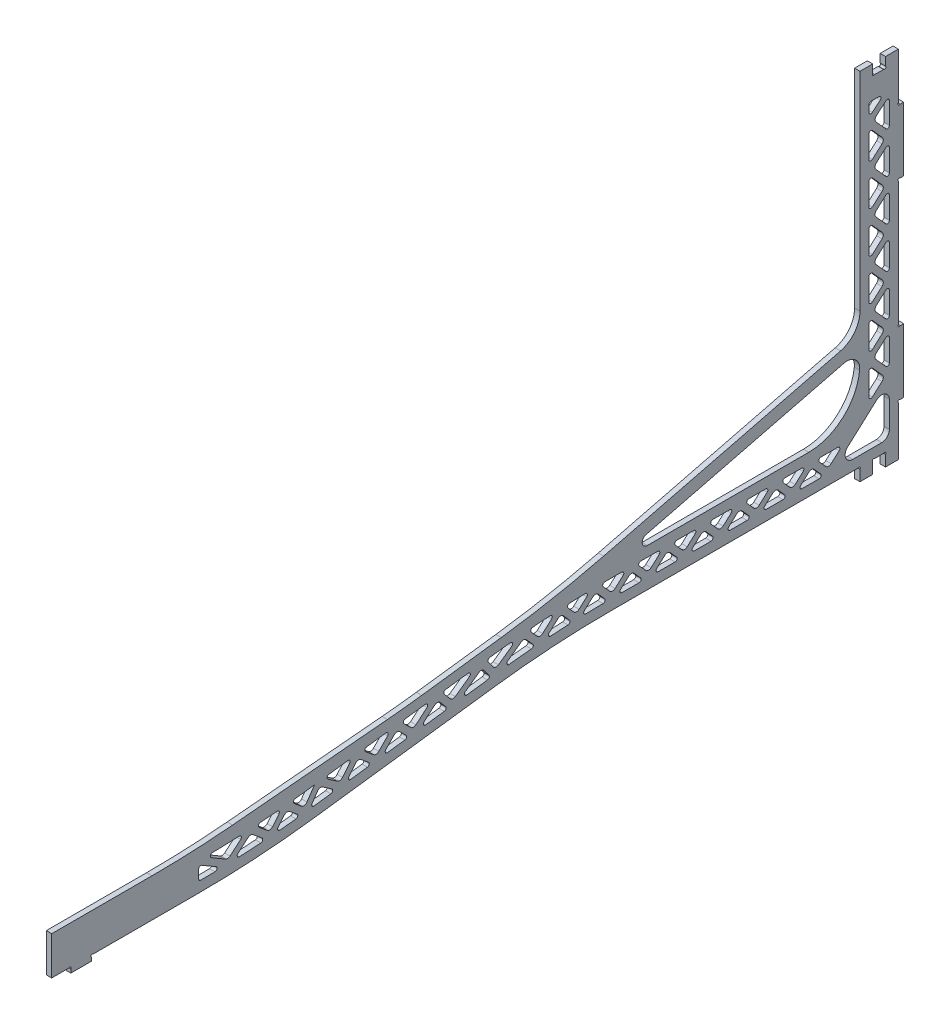
SolidWorks part; units mm, degrees
material "自定义塑料碳纤维-1.6"
ref_plane "前视基准面" through (0, 0, 0) normal (0, 0, 1) x (1, 0, 0)
ref_plane "上视基准面" through (0, 0, 0) normal (0, 1, 0) x (1, 0, 0)
ref_plane "右视基准面" through (0, 0, 0) normal (1, 0, 0) x (0, 0, -1)
other "Configuration Table"
sketch "草图2" plane through (0, 0, 0) normal (1, 0, 0) x (0, 0, -1)
  line L0 (0, 0) -> (331, 0)
  line L1 (331, 0) -> (331, 130)
  line L2 (331, 130) -> (316, 130)
  line L3 (316, 130) -> (316, 15)
  line L4 (316, 15) -> (0, 15)
  line L5 (0, 15) -> (0, 0)
  line L6 (331, 0) -> (331, -5)
  line L7 (331, -5) -> (326, -5)
  line L8 (326, -5) -> (326, 0)
  line L9 (321, 0) -> (321, -5)
  line L10 (321, -5) -> (316, -5)
  line L11 (316, -5) -> (316, 0)
  line L12 (331, 130) -> (331, 134)
  line L13 (331, 134) -> (326, 134)
  line L14 (326, 134) -> (326, 130)
  line L15 (80, 0) -> (196, 15)
  line L16 (196, 15) -> (196, 0) construction
  line L17 (196, 0) -> (80, -15)
  line L18 (80, -15) -> (0, -15)
  line L19 (0, -15) -> (0, 0)
  line L20 (80, 0) -> (80, -15) construction
  line L21 (55, 0) -> (138, 7.5)
  line L22 (316, 130) -> (316, 134)
  line L23 (316, 134) -> (321, 134)
  line L24 (321, 134) -> (321, 130)
  dimension "D1" = 15
  dimension "D2" = 130
  dimension "D3" = 15
  dimension "D4" = 331
  dimension "D5" = 4
  dimension "D6" = 5
  dimension "D7" = 5
  dimension "D8" = 5
  dimension "D9" = 5
  dimension "D10" = 5
  dimension "D11" = 120
  dimension "D12" = 15
  dimension "D13" = 80
  dimension "D14" = 25
  dimension "D15" = 5
extrude "凸台-拉伸1" add sketch "草图2" along normal mid plane 2.1 contours L19 L18 L17 L0 | L15 L0 L1 L2 L3 L4 | L13 L14 L2 L12 | L8 L7 L6 L0 | L11 L10 L9 L0 | L21 L0 L15 | L24 L23 L22 L2 region at (0, -6.4493, -73.0628) region at (0, 2.5, -91) region at (0, 0.9467, -109.3625) region at (0, -2.5, -318.5) region at (0, 132, -318.5) region at (0, -2.5, -328.5) region at (0, 132, -328.5)
sketch "草图3" plane through (1.05, 0, 0) normal (1, 0, 0) x (0, 0, -1)
  line L0 (331, 40) -> (333.1, 40)
  line L1 (331, -5) -> (331, 134) construction
  line L2 (333.1, 40) -> (333.1, 15)
  line L3 (333.1, 15) -> (331, 15)
  line L4 (331, 115) -> (333.1, 115)
  line L5 (331, -5) -> (331, 134) construction
  line L6 (333.1, 115) -> (333.1, 90)
  line L7 (333.1, 90) -> (331, 90)
  line L8 (331, 90) -> (331, 115)
  line L9 (331, 40) -> (331, 15)
  line L10 (316, 130) -> (316, 0)
  line L11 (331, 65) -> (316, 65)
  line L12 (331, 90) -> (331, 40)
  line L13 (326, 130) -> (316, 130)
  line M10 (331, -5) -> (331, 134)
  dimension "D2" = 50
  dimension "D3" = 25
  dimension "D4" = 25
  dimension "D5" = 2.1
extrude "凸台-拉伸2" add sketch "草图3" against normal up to surface (2.1 mm away) contours L7 L6 L4 M10 | L3 L2 L0 M10 region at (1.05, 27.5, -332.05) region at (1.05, 102.5, -332.05) up to face at (-1.05, 37.3095, -246.619)
fillet "圆角1" radius 20 1 edges at (0, 15, -316)
sketch "草图5" plane through (-1.05, 0, 0) normal (-1, 0, 0) x (0, 0, 1)
  line L0 (-316, 45) -> (-196, 15)
  line L1 (-316, 134) -> (-316, 35) construction
  line L2 (-296, 15) -> (-196, 15) construction
  dimension "D1" = 120
  dimension "D2" = 30
extrude "拉伸-薄壁1" add sketch "草图5" against normal up to surface (2.1 mm away) thin up to face at (1.05, 44.4786, -271.1847) thin type one direction wall 5
fillet "圆角2" radius 10 1 edges at (0, 45, -316)
fillet "圆角3" radius 5 1 edges at (0, 39.8461, -316)
fillet "圆角4" radius 2 1 edges at (0, 15, -216.6155)
fillet "圆角5" radius 350 5 edges at (0, 15, -196) (0, -15, -80) (0, 0, -196) (0, 7.5, -138) (0, 0, -55)
sketch "草图6" plane through (1.05, 0, 0) normal (1, 0, 0) x (0, 0, -1)
  line L0 (316, 130) -> (331, 130) construction
  line L1 (319.5, 121.6838) -> (327.5, 121.6838)
  line L2 (319.5, 121.6838) -> (319.5, 10)
  line L3 (319.5, 10) -> (327.5, 10)
  line L4 (327.5, 121.6838) -> (327.5, 10)
  line L5 (323.5, 10) -> (323.5, 121.6838) construction
  line L6 (319.5, 65.8419) -> (327.5, 65.8419) construction
  line L7 (331, 115) -> (331, 134) construction
  line L8 (323.5, 121.6838) -> (323.5, 130) construction
  line L9 (218.5355, 0) -> (316, 0) construction
  line L10 (316, 134) -> (316, 52.8078) construction
  line L11 (326, 130) -> (321, 130) construction
  point P0 (323.5, 65.8419)
  dimension "D1" = 8
  dimension "D2" = 8.3162
  dimension "D3" = 10
extrude "切除-拉伸1" cut sketch "草图6" against normal blind 10
sketch "草图7" plane through (1.05, 0, 0) normal (1, 0, 0) x (0, 0, -1)
  line L34 (316, 11) -> (218.5355, 11)
  line L35 (172.2399, 8.0192) -> (100.9387, -1.2008)
  line L36 (57.4645, -4) -> (0, -4)
  line L37 (316, 4) -> (218.5355, 4)
  line L38 (173.1376, 1.077) -> (101.8364, -8.143)
  line L39 (57.4645, -11) -> (0, -11)
  line L40 (316, 4) -> (218.5355, 4)
  line L41 (173.1376, 1.077) -> (101.8364, -8.143)
  line L42 (57.4645, -11) -> (0, -11)
  line L43 (309.5, 11) -> (319.5, 20)
  line L44 (319.5, 121.6838) -> (319.5, 10) construction
  line L45 (327.5, 10) -> (327.5, 4)
  line L46 (327.5, 4) -> (316, 4)
  line L47 (319.5, 10) -> (327.5, 10) construction
  line L48 (327.5, 10) -> (319.5, 20)
  line L49 (57.4645, -4) -> (57.4645, -11)
  arc A12 (218.5355, 11) -> (172.2399, 8.0192) centre (218.5355, -350) ccw
  arc A13 (57.4645, -4) -> (100.9387, -1.2008) centre (57.4645, 335) ccw
  arc A18 (218.5355, 4) -> (173.1376, 1.077) centre (218.5355, -350) ccw
  arc A19 (57.4645, -11) -> (101.8364, -8.143) centre (57.4645, 335) ccw
  arc A20 (218.5355, 4) -> (173.1376, 1.077) centre (218.5355, -350) ccw
  arc A21 (57.4645, -11) -> (101.8364, -8.143) centre (57.4645, 335) ccw
  line M28 (327.5, 10) -> (319.5, 10)
  line M29 (319.5, 10) -> (319.5, 121.6838)
  dimension "D3" = 10
  dimension "D4" = 10
  dimension "D1" = 4
  dimension "D2" = 7
extrude "切除-拉伸2" cut sketch "草图7" against normal blind 10 contours L49 A21 L41 A20 L40 L46 L45 L43 L34 A12 L35 A13 M28 M29 region at (1.05, 3.2645, -194.6514)
sketch "草图8" plane through (1.05, 0, 0) normal (1, 0, 0) x (0, 0, -1)
  line L0 (303.516, 4) -> (327.5, 25.5856)
  line L1 (327.5, 4) -> (327.5, 121.6838) construction
  line L2 (327.5, 25.5856) -> (319.5, 34.4745)
  line L3 (319.5, 121.6838) -> (319.5, 20) construction
  line L4 (319.5, 34.4745) -> (327.5, 41.6745)
  line L5 (327.5, 41.6745) -> (319.5, 50.5633)
  line L6 (319.5, 50.5633) -> (327.5, 57.7633)
  line L7 (327.5, 57.7633) -> (319.5, 66.6522)
  line L8 (319.5, 66.6522) -> (327.5, 73.8522)
  line L9 (327.5, 73.8522) -> (319.5, 82.7411)
  line L10 (319.5, 82.7411) -> (327.5, 89.9411)
  line L11 (327.5, 89.9411) -> (319.5, 98.83)
  line L12 (319.5, 98.83) -> (327.5, 106.03)
  line L13 (327.5, 106.03) -> (319.5, 114.9189)
  line L14 (319.5, 114.9189) -> (327.5, 121.6838)
  line L15 (57.4645, -4) -> (57.4645, -11) construction
  line L16 (309.5, 11) -> (319.5, 20) construction
  line L18 (327.5, 4) -> (218.5355, 4) construction
  line L19 (303.516, 4) -> (297.216, 11)
  line L20 (309.5, 11) -> (218.5355, 11) construction
  line L21 (297.216, 11) -> (289.4383, 4)
  line L22 (289.4383, 4) -> (283.1383, 11)
  line L23 (283.1383, 11) -> (275.3605, 4)
  line L24 (275.3605, 4) -> (269.0605, 11)
  line L25 (269.0605, 11) -> (261.2827, 4)
  line L26 (261.2827, 4) -> (254.9827, 11)
  line L27 (254.9827, 11) -> (247.2049, 4)
  line L28 (247.2049, 4) -> (240.9049, 11)
  line L29 (240.9049, 11) -> (233.1271, 4)
  line L30 (233.1271, 4) -> (226.8271, 11)
  line L31 (226.8271, 11) -> (219.0494, 4)
  line L32 (219.0494, 4) -> (212.7494, 11)
  line L33 (212.7494, 11) -> (204.9716, 4)
  line L34 (204.9716, 4) -> (199.1408, 10.4786)
  line L35 (199.1408, 10.4786) -> (190.7268, 2.906)
  line L36 (190.7268, 2.906) -> (184.8591, 9.4258)
  line L37 (184.8591, 9.4258) -> (173.1376, 1.077)
  line L38 (173.1376, 1.077) -> (168.5469, 7.5222)
  line L39 (168.5469, 7.5222) -> (156.4724, -1.078)
  line L40 (156.4724, -1.078) -> (151.0504, 5.2791)
  line L41 (151.0504, 5.2791) -> (141.2959, -3.0405)
  line L42 (141.2959, -3.0405) -> (134.9562, 3.198)
  line L43 (134.9562, 3.198) -> (126.998, -4.8894)
  line L44 (126.998, -4.8894) -> (119.6055, 1.213)
  line L45 (119.6055, 1.213) -> (113.0828, -6.6888)
  line L46 (173.1376, 1.077) -> (101.8364, -8.143) construction
  line L47 (113.0828, -6.6888) -> (104.4497, -0.7468)
  line L48 (172.2399, 8.0192) -> (100.9387, -1.2008) construction
  line L49 (104.4497, -0.7468) -> (99.117, -8.4947)
  line L50 (99.117, -8.4947) -> (91.7245, -2.3923)
  line L51 (91.7245, -2.3923) -> (85.5624, -9.8572)
  line L52 (85.5624, -9.8572) -> (77.7322, -3.3936)
  line L53 (77.7322, -3.3936) -> (69.0411, -10.8063)
  line L54 (69.0411, -10.8063) -> (57.4645, -4)
  arc A0 (218.5355, 4) -> (173.1376, 1.077) centre (218.5355, -350) ccw construction
  arc A1 (218.5355, 11) -> (172.2399, 8.0192) centre (218.5355, -350) ccw construction
  arc A2 (57.4645, -4) -> (100.9387, -1.2008) centre (57.4645, 335) ccw construction
  arc A3 (57.4645, -11) -> (101.8364, -8.143) centre (57.4645, 335) ccw construction
  dimension "D2" = 1.2
  dimension "D3" = 100
  dimension "D4" = 90
  dimension "D5" = 85
  dimension "D6" = 95
  dimension "D7" = 95
  dimension "D8" = 95
  dimension "D9" = 95
extrude "拉伸-薄壁2" add sketch "草图8" against normal up to surface (2.1 mm away) thin up to face at (-1.05, 39.8176, -251.717) thin type mid plane wall 2.5
fillet "圆角6" radius 3 3 edges at (0, 4, -327.5) (0, 4, -305.3846) (0, 23.9039, -327.5)
fillet "圆角7" radius 0.8 27 edges at (0, 121.6838, -319.5) (0, 113.0503, -319.5) (0, 96.9615, -319.5) (0, 80.8726, -319.5) (0, 64.7837, -319.5) (0, 48.6948, -319.5) (0, 107.8986, -327.5) (0, 91.8097, -327.5) (0, 75.7208, -327.5) (0, 59.6319, -327.5) (0, 43.543, -327.5) (0, 116.5559, -319.5) (0, 100.5117, -319.5) (0, 84.4228, -319.5) (0, 68.3339, -319.5) (0, 52.245, -319.5) (0, 36.1562, -319.5) (0, 120.0468, -327.5) (0, 104.3483, -327.5) (0, 88.2594, -327.5) (0, 72.1705, -327.5) (0, 56.0816, -327.5) (0, 39.9928, -327.5) (0, 32.6059, -319.5) (0, 27.4541, -327.5) (0, 20.0673, -319.5) (0, 121.6838, -325.5641)
fillet "圆角8" radius 1.5 12 edges at (0, 90.034, -325.7347) (0, 73.9451, -325.7347) (0, 57.8563, -325.7347) (0, 41.7674, -325.7347) (0, 50.4704, -321.2653) (0, 66.5593, -321.2653) (0, 82.6482, -321.2653) (0, 98.7371, -321.2653) (0, 106.1229, -325.7347) (0, 114.7969, -321.2915) (0, 25.6785, -325.7347) (0, 34.3815, -321.2653)
fillet "圆角9" radius 0.8 68 edges at (0, 4, -263.1513) (0, 4, -277.229) (0, 4, -291.3068) (0, 4, -249.0735) (0, 4, -234.9957) (0, 4, -220.9179) (0, 3.7993, -206.6172) (0, 1.4053, -175.7532) (0, 3.0609, -192.7675) (0, -0.7376, -159.105) (0, -2.7469, -143.5664) (0, -4.6295, -129.0074) (0, -6.4541, -114.8973) (0, -9.7109, -87.3041) (0, -10.7331, -71.0532) (0, -10.8769, -66.6949) (0, -9.9986, -83.7701) (0, -6.9288, -111.2267) (0, -5.1089, -125.3004) (0, -3.2442, -139.7208) (0, -1.2694, -154.9927) (0, 0.8952, -171.7324) (0, 2.779, -189.1594) (0, 3.6837, -203.5745) (0, 4, -231.4454) (0, 4, -245.5232) (0, 4, -259.601) (0, 4, -273.6788) (0, 4, -287.7566) (0, 4, -301.8343) (0, 11, -284.82) (0, 11, -298.8977) (0, 11, -270.7422) (0, 11, -256.6644) (0, 11, -242.5866) (0, 11, -228.5089) (0, 10.9769, -214.4519) (0, 10.5615, -200.7479) (0, 9.568, -186.4128) (0, 7.7217, -169.9394) (0, 5.4705, -152.5301) (0, 3.4017, -136.5314) (0, 1.4325, -121.3031) (0, -0.5068, -106.3058) (0, -2.0973, -93.3307) (0, -3.2793, -79.5574) (0, -3.9911, -59.9158) (0, -3.5109, -75.6685) (0, -2.4279, -90.0743) (0, 0.9783, -117.7909) (0, 2.9382, -132.9468) (0, 4.9855, -148.7799) (0, 7.2055, -165.9476) (0, 9.1833, -182.364) (0, 10.3658, -197.1469) (0, 10.9169, -210.7884) (0, 11, -224.9586) (0, 11, -239.0364) (0, 11, -253.1141) (0, 11, -267.1919) (0, 11, -281.2697) (0, 11, -295.3475) (0, 11, -309.4253) (0, 3.9981, -217.3694) (0, -8.6889, -97.3888) (0, -8.2775, -100.784) (0, -11, -57.4645) (0, -5.45, -57.4645)
fillet "圆角10" radius 1.5 33 edges at (0, 9.2347, -283.0453) (0, 9.2347, -297.1231) (0, 9.2347, -268.9676) (0, 9.2347, -254.8898) (0, 9.2347, -240.812) (0, 9.2347, -226.7342) (0, 9.2347, -212.6565) (0, 8.7133, -199.0479) (0, 7.7607, -184.676) (0, 5.7789, -168.2539) (0, 3.5169, -150.9105) (0, 1.4303, -134.9704) (0, -2.4852, -104.7707) (0, -4.1521, -91.8928) (0, -5.0253, -77.7454) (0, -8.0975, -85.3942) (0, -9.2775, -68.9073) (0, -6.6623, -98.8608) (0, -5.0097, -112.8479) (0, -3.1962, -126.9104) (0, -1.3461, -141.3563) (0, 0.6046, -156.6802) (0, 2.8203, -173.4306) (0, 4.6714, -190.8197) (0, 5.7653, -205.0645) (0, 5.7653, -219.1423) (0, 5.7653, -233.2201) (0, 5.7653, -247.2978) (0, 5.7653, -261.3756) (0, 5.7653, -275.4534) (0, 5.7653, -289.5312) (0, 5.7653, -303.609) (0, -0.5468, -119.7737)
sketch "草图9" plane through (1.05, 0, 0) normal (1, 0, 0) x (0, 0, -1)
  line L0 (316, -0.7071) -> (315.2929, 0)
  line L1 (218.5355, 0) -> (316, 0) construction
  line L2 (321.7071, 0) -> (321, -0.7071)
  line L3 (321, 0) -> (321, -5) construction
  line L4 (326, -0.7071) -> (325.2929, 0)
  line L5 (326, -5) -> (326, 0) construction
  line L6 (321, 0) -> (326, 0) construction
  line L7 (331.7071, 15) -> (331, 14.2929)
  line L8 (321.7071, 130) -> (321, 130.7071)
  line L9 (331, -5) -> (331, 15) construction
  line L10 (331.7071, 40) -> (331, 40.7071)
  line L11 (321.3536, 130.3536) -> (321, 130)
  line L12 (331.7071, 90) -> (331, 89.2929)
  line L13 (326, 130) -> (321, 130) construction
  line L14 (331, 115.7071) -> (331.7071, 115)
  line L15 (331, 115) -> (331, 134) construction
  line L17 (326, 130.7071) -> (325.2929, 130)
  line L18 (326, 134) -> (326, 130) construction
  line L19 (325.6464, 130.3536) -> (326, 130)
  line L20 (316, 0) -> (315.6464, -0.3536)
  line L21 (321.3536, -0.3536) -> (321, 0)
  line L22 (325.6464, -0.3536) -> (326, 0)
  line L23 (331.3536, 40.3536) -> (331, 40)
  line L24 (331.3536, 14.6464) -> (331, 15)
  line L25 (331.3536, 115.3536) -> (331, 115)
  line L26 (331.3536, 89.6464) -> (331, 90)
  line L27 (331, 40) -> (331, 90) construction
  line L28 (331, 40) -> (333.1, 40) construction
  line L29 (333.1, 90) -> (331, 90) construction
  circle A0 centre (325.6464, -0.3536) radius 0.5
  circle A1 centre (321.3536, -0.3536) radius 0.5
  circle A2 centre (315.6464, -0.3536) radius 0.5
  circle A3 centre (331.3536, 14.6464) radius 0.5
  circle A4 centre (331.3536, 40.3536) radius 0.5
  circle A5 centre (331.3536, 89.6464) radius 0.5
  circle A6 centre (331.3536, 115.3536) radius 0.5
  circle A7 centre (325.6464, 130.3536) radius 0.5
  circle A8 centre (321.3536, 130.3536) radius 0.5
  dimension "D1" = 1
extrude "切除-拉伸3" cut sketch "草图9" against normal up to surface (2.1 mm away) contours L19 A7 L17 | L17 A7 L19 | L25 A6 L14 | L14 A6 L25 | L26 A5 L12 | L12 A5 L26 | L23 A4 L10 | L10 A4 L23 | L24 A3 L7 | L7 A3 L24 | L4 A0 L22 | L22 A0 L4 | L2 A1 L21 | L21 A1 L2 | L20 A2 L0 | L0 A2 L20 | L11 A8 L8 | L8 A8 L11 region at (1.05, -0.3536, -315.9466) region at (1.05, -0.0534, -315.6464) region at (1.05, -0.0534, -321.3536) region at (1.05, -0.3536, -321.0534) region at (1.05, -0.3536, -325.9466) region at (1.05, -0.0534, -325.6464) region at (1.05, 14.9466, -331.3536) region at (1.05, 14.6464, -331.0534) region at (1.05, 130.0534, -321.3536) region at (1.05, 130.3536, -321.0534) region at (1.05, 40.0534, -331.3536) region at (1.05, 40.3536, -331.0534) region at (1.05, 89.9466, -331.3536) region at (1.05, 89.6464, -331.0534) region at (1.05, 115.3536, -331.0534) region at (1.05, 115.0534, -331.3536) region at (1.05, 130.3536, -325.9466) region at (1.05, 130.0534, -325.6464) up to face at (-1.05, -9.0955, -60.0353)
fillet "圆角11" radius 0.3 18 edges at (0, 130.7071, -326) (0, 130, -325.2929) (0, 130.7071, -321) (0, 130, -321.7071) (0, -0.7071, -316) (0, 0, -315.2929) (0, -0.7071, -321) (0, 0, -321.7071) (0, -0.7071, -326) (0, 0, -325.2929) (0, 15, -331.7071) (0, 14.2929, -331) (0, 40.7071, -331) (0, 40, -331.7071) (0, 90, -331.7071) (0, 89.2929, -331) (0, 115.7071, -331) (0, 115, -331.7071)
sketch "草图10" plane through (1.05, 0, 0) normal (1, 0, 0) x (0, 0, -1)
  line L0 (7.5, -15) -> (7.5, -17.1)
  line L1 (57.4645, -15) -> (0, -15) construction
  line L2 (7.5, -17.1) -> (15.5, -17.1)
  line L3 (15.5, -17.1) -> (15.5, -15)
  line L4 (15.5, -15) -> (7.5, -15)
  line L5 (0, -15) -> (0, 0) construction
  dimension "D1" = 2.1
  dimension "D2" = 8
  dimension "D3" = 7.5
extrude "凸台-拉伸3" add sketch "草图10" against normal up to surface (2.1 mm away) up to face at (-1.05, -9.0955, -60.0353)
sketch "草图11" plane through (1.05, 0, 0) normal (1, 0, 0) x (0, 0, -1)
  line L0 (15.8536, -15.3536) -> (15.5, -15)
  line L1 (7.1464, -15.3536) -> (7.5, -15)
  line L2 (7.5, -15) -> (0, -15) construction
  line L3 (57.4645, -15) -> (15.5, -15) construction
  circle A0 centre (15.8536, -15.3536) radius 0.5
  circle A1 centre (7.1464, -15.3536) radius 0.5
  dimension "D1" = 1
  dimension "D2" = 45
  dimension "D3" = 45
extrude "切除-拉伸4" cut sketch "草图11" against normal through all contours A0 | A1 region at (1.05, -15.8024, -15.6676) region at (1.05, -15.5395, -6.6976)
fillet "圆角12" radius 0.3 4 edges at (0, -15.7071, -7.5) (0, -15.7071, -15.5) (0, -15, -16.2071) (0, -15, -6.7929)
